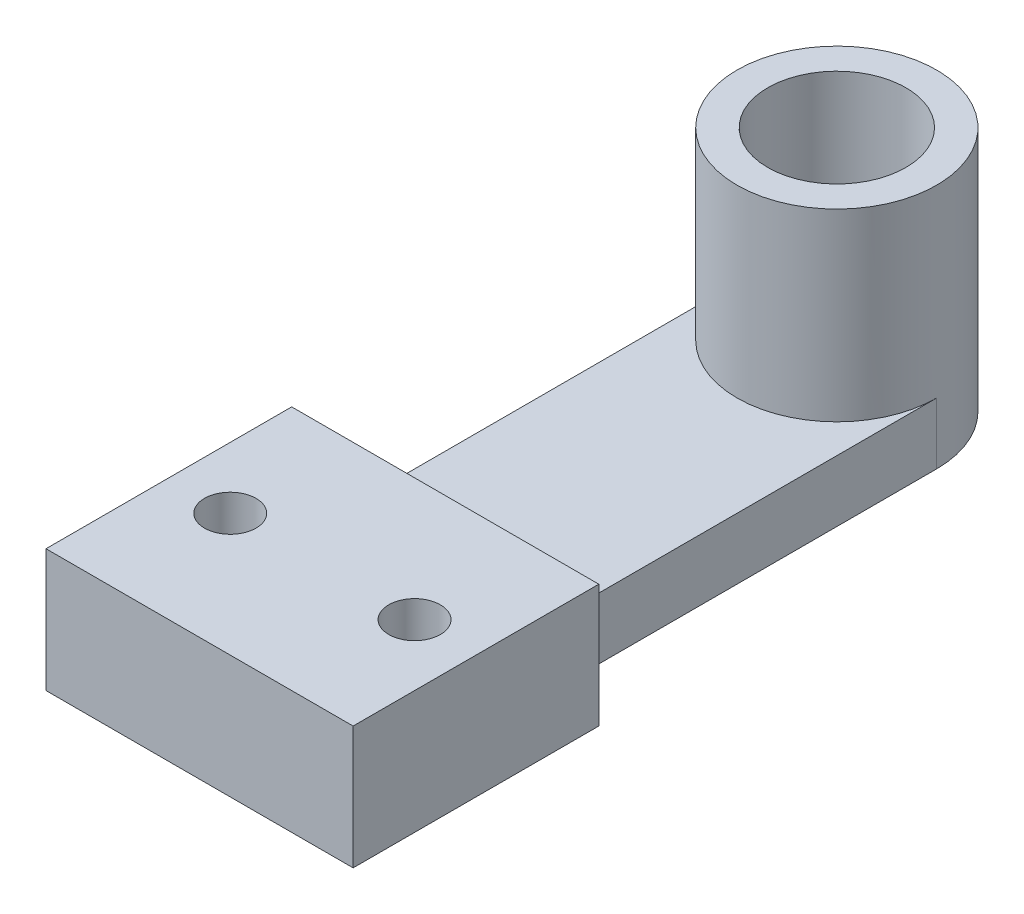
SolidWorks part; units mm, degrees
ref_plane "Front Plane" through (0, 0, 0) normal (0, 0, 1) x (1, 0, 0)
ref_plane "Top Plane" through (0, 0, 0) normal (0, 1, 0) x (1, 0, 0)
ref_plane "Right Plane" through (0, 0, 0) normal (1, 0, 0) x (0, 0, -1)
sketch "Sketch1" plane through (0, 0, 0) normal (0, 1, 0) x (1, 0, 0)
  line L1 (-12.5, -10) -> (12.5, -10)
  line L2 (-12.5, -10) -> (-12.5, 10)
  line L3 (-12.5, 10) -> (12.5, 10)
  line L4 (12.5, -10) -> (12.5, 10)
  line L5 (-12.5, -10) -> (12.5, 10) construction
  line L6 (-12.5, 10) -> (12.5, -10) construction
  line L7 (-8.125, 10) -> (8.125, 10)
  line L8 (-8.125, 10) -> (-8.125, 50)
  line L9 (-8.125, 50) -> (8.125, 50)
  line L10 (8.125, 10) -> (8.125, 50)
  line L11 (-8.125, 10) -> (8.125, 50) construction
  line L12 (-8.125, 50) -> (8.125, 10) construction
  circle A1 centre (0, 41.875) radius 8.125
  circle A2 centre (0, 41.875) radius 5.625
  circle A3 centre (-7.5, 0) radius 2.1
  circle A4 centre (7.5, 0) radius 2.1
  point P0 (0, 0)
  point P10 (0, 30)
  point P18 (-8.125, 0)
  point P19 (0, 0)
  point P20 (0, 0)
  dimension "D3" = 11.25
  dimension "D4" = 2.5
  dimension "D5" = 4.2
  dimension "D1" = 40
  dimension "D2" = 20
  dimension "D6" = 15
  dimension "D7" = 25
  dimension "D8" = 7.5
extrude "Boss-Extrude1" add sketch "Sketch1" along normal blind 5 contours L1 L4 L3 L2 A4 A3 | A1 A2 | A1 L8 L3 L10 | A2 region at (0, 0, 0) region at (0, 0, -22.8113) region at (-5.5827, 0, -47.4577) region at (0, 0, -41.875)
extrude "Boss-Extrude2" add sketch "Sketch1<3>" along normal blind 10 contours L1 L4 L3 L2 A4 A3 region at (0, 0, 0)
sketch "Sketch1<3>" plane through (0, 0, 0) normal (0, 1, 0) x (1, 0, 0) same geometry as "Sketch1"
extrude "Boss-Extrude3" add sketch "Sketch1<4>" along normal blind 20 contours A1 A2 region at (-5.5827, 0, -47.4577)
sketch "Sketch1<4>" plane through (0, 0, 0) normal (0, 1, 0) x (1, 0, 0) same geometry as "Sketch1"
equation "\"m3 hole\"= 3.2"
equation "\"m4 hole\"= 4.2"
equation "\"m5 hole\"= 5.2"
equation "\"m6 hole\"= 6.2"
equation "\"m8 hole\"= 8.2"
equation "\"m3 tapped\"= 2.5"
equation "\"m4 tapped\"= 3.3"
equation "\"m5 tapped\"= 4.2"
equation "\"m6 tapped\"= 5"
equation "\"m8 tapped\"= 6.8"
